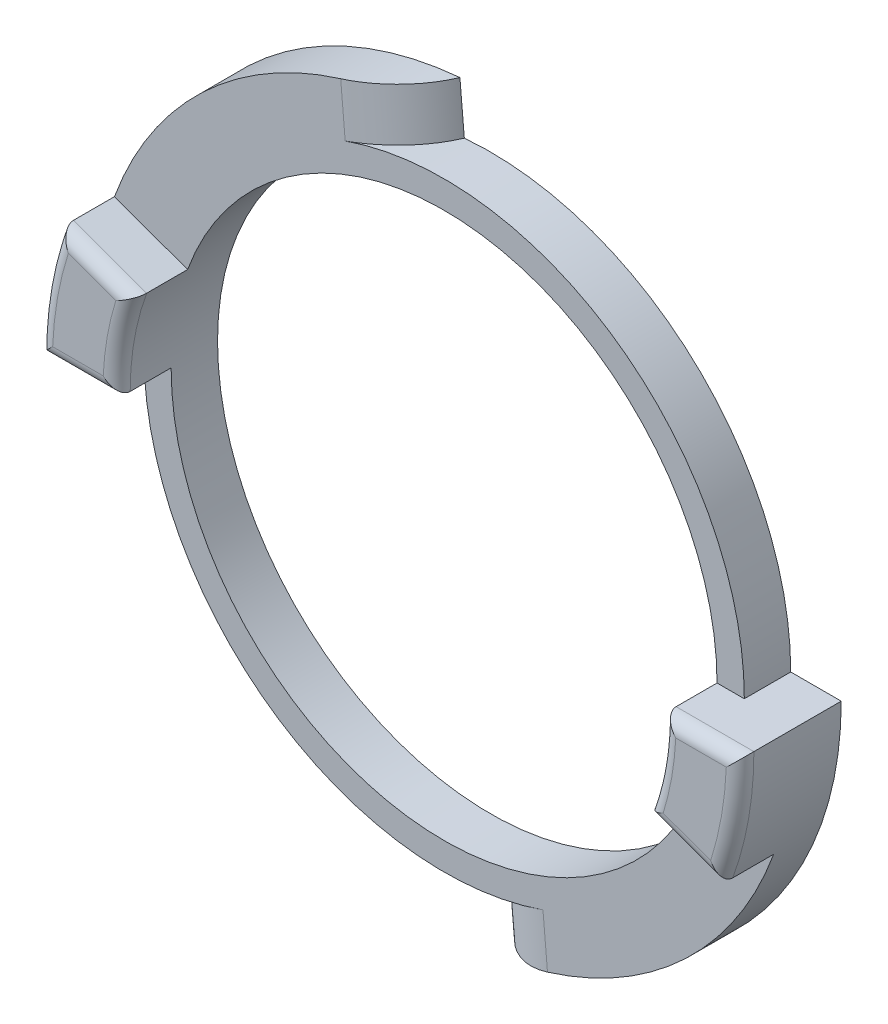
SolidWorks part; units mm, degrees
ref_plane "Front Plane" through (0, 0, 0) normal (0, 0, 1) x (1, 0, 0)
ref_plane "Top Plane" through (0, 0, 0) normal (0, 1, 0) x (1, 0, 0)
ref_plane "Right Plane" through (0, 0, 0) normal (1, 0, 0) x (0, 0, -1)
sketch "Sketch1" plane through (0, 0, 0) normal (0, 0, 1) x (1, 0, 0)
  line L0 (0, 0) -> (-1.3829, 15.8061)
  line L1 (0, 0) -> (1.2667, -14.4789)
  line L2 (0, 11.15) -> (0, 13) construction
  line L3 (0, -11.15) -> (0, -13) construction
  line L4 (0, 0) -> (-13.6469, 0)
  line L5 (0, 0) -> (13.562, 0)
  circle A0 centre (0, 0) radius 12.85
  circle A1 centre (0, 0) radius 10
  circle A2 centre (0, 0) radius 10
  circle A3 centre (0, 0) radius 11
  dimension "D1" = 25.7
  dimension "D2" = 20
  dimension "D3" = 5
  dimension "D4" = 5
extrude "Boss-Extrude1" add sketch "Sketch1" along normal blind 1.7 contours A3 L0 A0 L4 | L0 A3 L4 A1 | L5 A3 L0 A1 | L1 A3 L5 A1 | L4 A3 L1 A1 | A3 L1 A0 L5 region at (-7.4828, 6.8567, 0) region at (-0.7533, 10.4742, 0) region at (7.4828, -6.8567, 0) region at (0.7533, -10.4742, 0) region at (-8.2389, 7.5495, 0) region at (8.2389, -7.5495, 0)
fillet "Fillet1" radius 3 2 edges at (1.0393, -11.8796, 1.7) (-1.0393, 11.8796, 1.7)
sketch "Sketch2" plane through (0, 0, 1.7) normal (0, 0, 1) x (1, 0, 0)
  line L0 (0, 0) -> (-12.85, 0)
  line L1 (-12.85, 0) -> (12.85, 0)
  line L2 (0, 0) -> (12.5085, -4.5527)
  line L3 (12.5085, -4.5527) -> (-13.4671, 4.9016)
  circle A0 centre (0, 0) radius 10
  circle A1 centre (0, 0) radius 12.85
  arc M5 (3.7883, -12.2789) -> (12.85, 0) centre (0, 0) ccw
  line M6 (12.85, 0) -> (11, 0)
  arc M9 (-3.7883, 12.2789) -> (-12.85, 0) centre (0, 0) ccw
  line M10 (-12.85, 0) -> (-11, 0)
  circle M11 centre (0, 0) radius 10
  dimension "D1" = 20
extrude "Boss-Extrude2" add sketch "Sketch2" along normal blind 2 contours L3 L0 M11 M9 M10 | L2 L1 M11 M5 M6 region at (-11.2524, 1.9841, 1.7) region at (11.2524, -1.9841, 1.7)
fillet "Fillet2" radius 0.5 8 edges at (-9.8481, 1.7365, 3.7) (-10.736, 3.9076, 3.7) (-12.6548, 2.2314, 3.7) (-11.425, 0, 3.7) (9.8481, -1.7365, 3.7) (10.736, -3.9076, 3.7) (12.6548, -2.2314, 3.7) (11.425, 0, 3.7)
